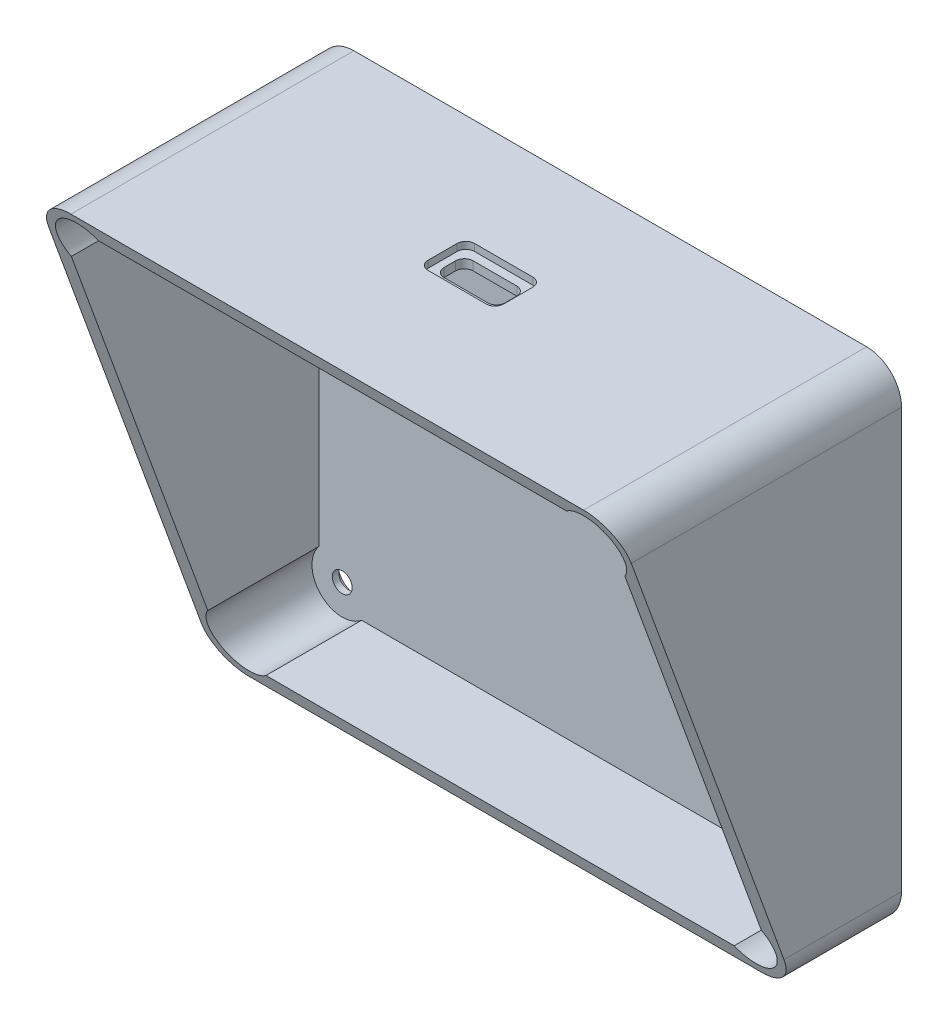
SolidWorks part; units mm, degrees
ref_plane "前视基准面" through (0, 0, 0) normal (0, 0, 1) x (1, 0, 0)
ref_plane "上视基准面" through (0, 0, 0) normal (0, 1, 0) x (1, 0, 0)
ref_plane "右视基准面" through (0, 0, 0) normal (1, 0, 0) x (0, 0, -1)
other "Configuration Table"
sketch "草图1" plane through (0, 0, 0) normal (0, 0, 1) x (1, 0, 0)
  line L0 (6, 0) -> (94, 0)
  line L1 (100, 6) -> (100, 78)
  line L2 (94, 84) -> (6, 84)
  line L3 (0, 78) -> (0, 6)
  arc A0 (94, 0) -> (100, 6) centre (94, 6) ccw
  arc A1 (100, 78) -> (94, 84) centre (94, 78) ccw
  arc A2 (6, 84) -> (0, 78) centre (6, 78) ccw
  arc A3 (0, 6) -> (6, 0) centre (6, 6) ccw
extrude "Outer_R6" add sketch "草图1" along normal blind 55
sketch "草图2" plane through (0, 0, 0) normal (0, 0, 1) x (1, 0, 0)
  line L0 (6, 2.5) -> (94, 2.5)
  line L1 (97.5, 6) -> (97.5, 78)
  line L2 (94, 81.5) -> (6, 81.5)
  line L3 (2.5, 78) -> (2.5, 6)
  arc A0 (94, 2.5) -> (97.5, 6) centre (94, 6) ccw
  arc A1 (97.5, 78) -> (94, 81.5) centre (94, 78) ccw
  arc A2 (6, 81.5) -> (2.5, 78) centre (6, 78) ccw
  arc A3 (2.5, 6) -> (6, 2.5) centre (6, 6) ccw
extrude "Cavity_floor2p5_wall2p5" cut sketch "草图2" along normal blind 65 from offset 2.5
sketch "草图3" plane through (0, 0, 0) normal (1, 0, 0) x (0, 0, -1)
  line L0 (-10.7206, -20) -> (-58.0367, 110)
  line L1 (-58.0367, 110) -> (-120, 110)
  line L2 (-120, 110) -> (-120, -20)
  line L3 (-120, -20) -> (-10.7206, -20)
extrude "Panel_seat_20deg" cut sketch "草图3" against normal through all and the other way through all
sketch "草图4" plane through (0, 0, 0) normal (0, 0, 1) x (1, 0, 0)
  circle A0 centre (6.5, 6.5) radius 5.2
extrude "Internal_post_clearance_0" cut sketch "草图4" along normal blind 60 from offset 2.5
sketch "草图5" plane through (0, 0, 0) normal (0, 0, 1) x (1, 0, 0)
  circle A0 centre (6.5, 6.5) radius 1.7
extrude "Underside_M3_0" cut sketch "草图5" along normal blind 3
sketch "草图6" plane through (0, 0, 0) normal (0, 0, 1) x (1, 0, 0)
  circle A0 centre (6.5, 6.5) radius 3.3
extrude "Underside_head_recess_0" cut sketch "草图6" along normal blind 1.4
sketch "草图7" plane through (0, 0, 0) normal (0, 0, 1) x (1, 0, 0)
  circle A0 centre (93.5, 6.5) radius 5.2
extrude "Internal_post_clearance_1" cut sketch "草图7" along normal blind 60 from offset 2.5
sketch "草图8" plane through (0, 0, 0) normal (0, 0, 1) x (1, 0, 0)
  circle A0 centre (93.5, 6.5) radius 1.7
extrude "Underside_M3_1" cut sketch "草图8" along normal blind 3
sketch "草图9" plane through (0, 0, 0) normal (0, 0, 1) x (1, 0, 0)
  circle A0 centre (93.5, 6.5) radius 3.3
extrude "Underside_head_recess_1" cut sketch "草图9" along normal blind 1.4
sketch "草图10" plane through (0, 0, 0) normal (0, 0, 1) x (1, 0, 0)
  circle A0 centre (6.5, 77.5) radius 5.2
extrude "Internal_post_clearance_2" cut sketch "草图10" along normal blind 60 from offset 2.5
sketch "草图11" plane through (0, 0, 0) normal (0, 0, 1) x (1, 0, 0)
  circle A0 centre (6.5, 77.5) radius 1.7
extrude "Underside_M3_2" cut sketch "草图11" along normal blind 3
sketch "草图12" plane through (0, 0, 0) normal (0, 0, 1) x (1, 0, 0)
  circle A0 centre (6.5, 77.5) radius 3.3
extrude "Underside_head_recess_2" cut sketch "草图12" along normal blind 1.4
sketch "草图13" plane through (0, 0, 0) normal (0, 0, 1) x (1, 0, 0)
  circle A0 centre (93.5, 77.5) radius 5.2
extrude "Internal_post_clearance_3" cut sketch "草图13" along normal blind 60 from offset 2.5
sketch "草图14" plane through (0, 0, 0) normal (0, 0, 1) x (1, 0, 0)
  circle A0 centre (93.5, 77.5) radius 1.7
extrude "Underside_M3_3" cut sketch "草图14" along normal blind 3
sketch "草图15" plane through (0, 0, 0) normal (0, 0, 1) x (1, 0, 0)
  circle A0 centre (93.5, 77.5) radius 3.3
extrude "Underside_head_recess_3" cut sketch "草图15" along normal blind 1.4
sketch "草图16" plane through (0, 0, 0) normal (0, 0, 1) x (1, 0, 0)
  circle A0 centre (37, 49) radius 2.2
  circle A1 centre (63, 49) radius 2.2
  circle A2 centre (37, 78) radius 2.2
  circle A3 centre (63, 78) radius 2.2
extrude "Centered_carrier_supports_Z7" add sketch "草图16" along normal blind 4.5 from offset 2.5
sketch "草图17" plane through (0, 0, 0) normal (0, 0, 1) x (1, 0, 0)
  circle A0 centre (37, 49) radius 1.15
  circle A1 centre (63, 49) radius 1.15
  circle A2 centre (37, 78) radius 1.15
  circle A3 centre (63, 78) radius 1.15
extrude "Carrier_M2_clearance" cut sketch "草图17" along normal blind 8
sketch "草图18" plane through (0, 0, 0) normal (0, 0, 1) x (1, 0, 0)
  circle A0 centre (37, 49) radius 2.2
  circle A1 centre (63, 49) radius 2.2
  circle A2 centre (37, 78) radius 2.2
  circle A3 centre (63, 78) radius 2.2
extrude "Carrier_head_recess" cut sketch "草图18" along normal blind 1.2
sketch "草图19" plane through (0, 0, 0) normal (0, 1, 0) x (1, 0, 0)
  line L0 (44.9, -20.25) -> (55.1, -20.25)
  line L1 (55.1, -20.25) -> (55.1, -24.33)
  line L2 (55.1, -24.33) -> (44.9, -24.33)
  line L3 (44.9, -24.33) -> (44.9, -20.25)
extrude "USB_C_centered_inner_opening" [suppressed] cut sketch "草图19" along normal blind 6 from offset 80
sketch "草图20" plane through (0, 0, 0) normal (0, 1, 0) x (1, 0, 0)
  line L0 (43.5, -18.29) -> (56.5, -18.29)
  line L1 (56.5, -18.29) -> (56.5, -26.29)
  line L2 (56.5, -26.29) -> (43.5, -26.29)
  line L3 (43.5, -26.29) -> (43.5, -18.29)
extrude "USB_C_cable_clearance_13x8" [suppressed] cut sketch "草图20" along normal blind 4 from offset 81
sketch "USB_Pocket_Backing_16x10_R2p5_Sketch" plane through (0, 0, 0) normal (0, 1, 0) x (1, 0, 0)
  line L0 (44.5, -27.29) -> (55.5, -27.29)
  line L1 (58, -24.79) -> (58, -19.79)
  line L2 (55.5, -17.29) -> (44.5, -17.29)
  line L3 (42, -19.79) -> (42, -24.79)
  arc A0 (55.5, -27.29) -> (58, -24.79) centre (55.5, -24.79) ccw
  arc A1 (58, -19.79) -> (55.5, -17.29) centre (55.5, -19.79) ccw
  arc A2 (44.5, -17.29) -> (42, -19.79) centre (44.5, -19.79) ccw
  arc A3 (42, -24.79) -> (44.5, -27.29) centre (44.5, -24.79) ccw
extrude "USB_Pocket_Backing_Y81p3_to84" add sketch "USB_Pocket_Backing_16x10_R2p5_Sketch" along normal blind 2.7 from offset 81.3
sketch "USB_Socket_Opening_10p5x5_R1p5_Sketch" plane through (0, 0, 0) normal (0, 1, 0) x (1, 0, 0)
  line L0 (46.25, -24.79) -> (53.75, -24.79)
  line L1 (55.25, -23.29) -> (55.25, -21.29)
  line L2 (53.75, -19.79) -> (46.25, -19.79)
  line L3 (44.75, -21.29) -> (44.75, -23.29)
  arc A0 (53.75, -24.79) -> (55.25, -23.29) centre (53.75, -23.29) ccw
  arc A1 (55.25, -21.29) -> (53.75, -19.79) centre (53.75, -21.29) ccw
  arc A2 (46.25, -19.79) -> (44.75, -21.29) centre (46.25, -21.29) ccw
  arc A3 (44.75, -23.29) -> (46.25, -24.79) centre (46.25, -23.29) ccw
extrude "USB_Socket_Opening_10p5x5_R1p5" cut sketch "USB_Socket_Opening_10p5x5_R1p5_Sketch" along normal blind 5 from offset 80.2
sketch "USB_Cable_Recess_13x8_R1p5_Sketch" plane through (0, 0, 0) normal (0, 1, 0) x (1, 0, 0)
  line L0 (45, -26.29) -> (55, -26.29)
  line L1 (56.5, -24.79) -> (56.5, -19.79)
  line L2 (55, -18.29) -> (45, -18.29)
  line L3 (43.5, -19.79) -> (43.5, -24.79)
  arc A0 (55, -26.29) -> (56.5, -24.79) centre (55, -24.79) ccw
  arc A1 (56.5, -19.79) -> (55, -18.29) centre (55, -19.79) ccw
  arc A2 (45, -18.29) -> (43.5, -19.79) centre (45, -19.79) ccw
  arc A3 (43.5, -24.79) -> (45, -26.29) centre (45, -24.79) ccw
extrude "USB_Cable_Recess_depth1p2_floor1p5" cut sketch "USB_Cable_Recess_13x8_R1p5_Sketch" along normal blind 2.2 from offset 82.8
